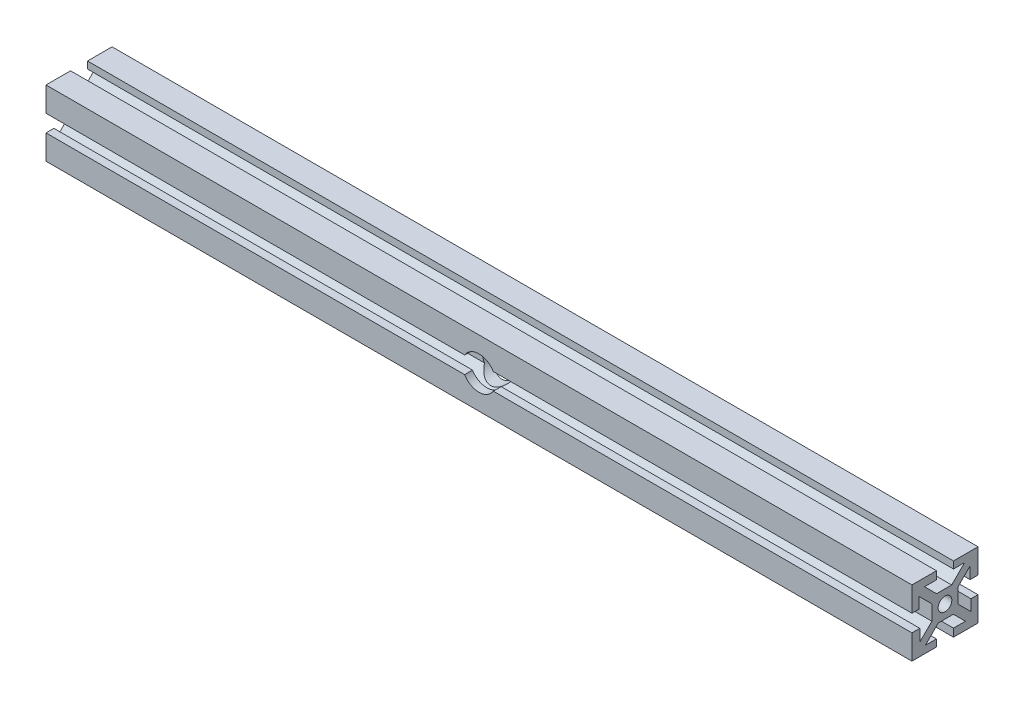
SolidWorks part; units mm, degrees
ref_plane "Front Plane" through (0, 0, 0) normal (0, 0, 1) x (1, 0, 0)
ref_plane "Top Plane" through (0, 0, 0) normal (0, 1, 0) x (1, 0, 0)
ref_plane "Right Plane" through (0, 0, 0) normal (1, 0, 0) x (0, 0, -1)
sketch "Sketch1" plane through (0, 0, 0) normal (1, 0, 0) x (0, 0, -1)
  line L0 (2.5534, 5) -> (7.4749, 9.9215)
  line L1 (-5, 5) -> (5, 5)
  line L2 (-5, 5) -> (-5, -5)
  line L3 (-5, -5) -> (5, -5)
  line L4 (5, 5) -> (5, -5)
  line L5 (-5, 5) -> (5, -5) construction
  line L6 (-5, -5) -> (5, 5) construction
  line L7 (7.4749, 9.9215) -> (9.5962, 7.8001)
  line L8 (9.5962, 7.8001) -> (5, 3.2039)
  line L9 (5, 5) -> (13.6489, 13.6489) construction
  line L10 (7.4749, 9.9215) -> (3.24, 9.9215)
  line L11 (3.24, 9.9215) -> (3.24, 12.5962)
  line L12 (3.24, 12.5962) -> (12.5962, 12.5962)
  line L13 (9.5962, 7.8001) -> (9.5962, 3.24)
  line L14 (9.5962, 3.24) -> (12.5962, 3.24)
  line L15 (12.5962, 3.24) -> (12.5962, 12.5962)
  line L17 (0, 0) -> (0, 24.089) construction
  line L18 (0, 0) -> (23.75, 0) construction
  circle A0 centre (0, 0) radius 2.605
  point P0 (0, 0)
  dimension "D1" = 5.21
  dimension "D2" = 10
  dimension "D3" = 10
  dimension "D4" = 3
  dimension "D5" = 1.27
  dimension "D6" = 6.5
  dimension "D7" = 3.24
  dimension "D8" = 3.24
  dimension "D9" = 3
extrude "Boss-Extrude1" add sketch "Sketch1" along normal blind 330.2 contours L4 L1 L2 L3 A0 | L8 L7 L0 L1 L4 | L14 L15 L12 L11 L10 L7 L13 region at (0, 4.8586, -3.7767) region at (0, 6.7479, -6.3823) region at (0, 9.18, -9.3105)
ref_axis "Axis1" through (0, 0, 0) along (1, 0, 0)
pattern_circular "CirPattern1" count 4 over 360 about axis through (0, 0, 0) along (1, 0, 0) of "Boss-Extrude1"
sketch "Sketch2" plane through (0, 0, 0) normal (0, 0, 1) x (1, 0, 0)
  circle A0 centre (165.1, 0) radius 6.35
  dimension "D2" = 12.7
  dimension "D1" = 165.1
extrude "Cut-Extrude1" cut sketch "Sketch2" along normal blind 20
